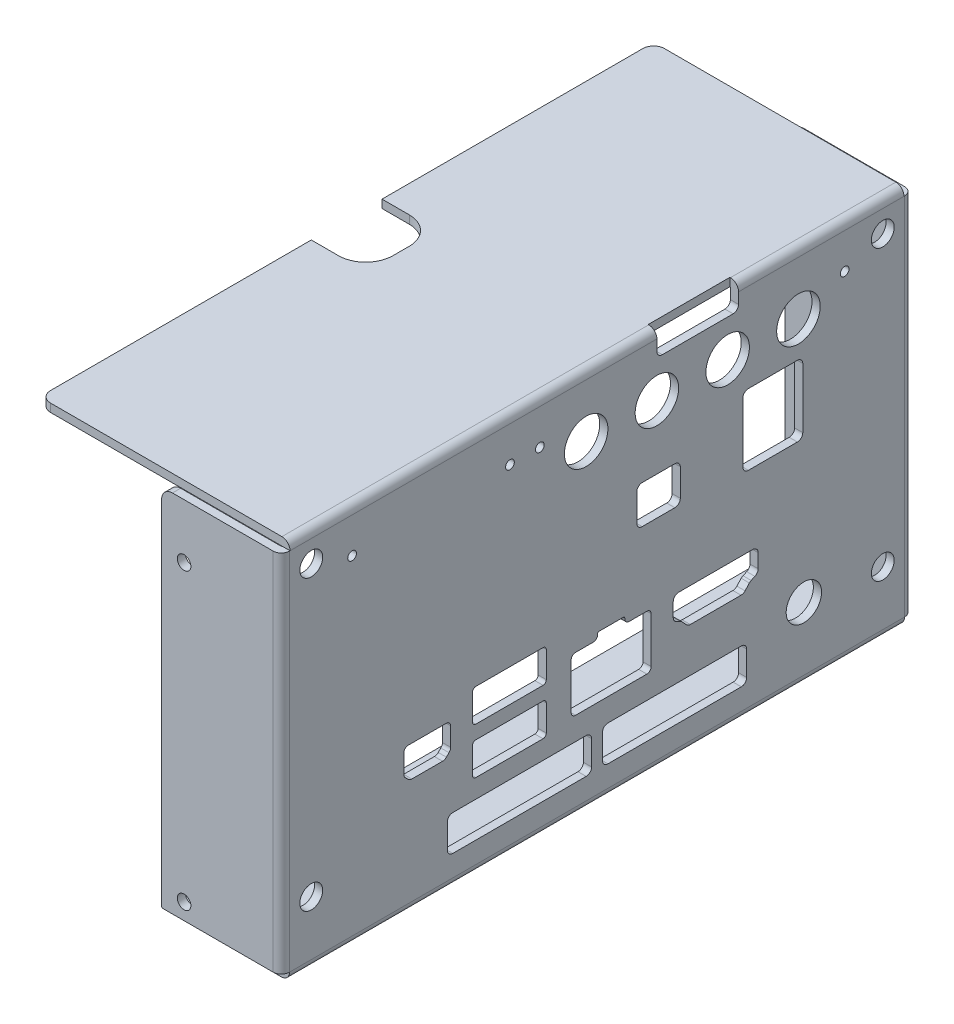
SolidWorks part; units mm, degrees
ref_plane "Alzado" through (0, 0, 0) normal (0, 0, 1) x (1, 0, 0)
ref_plane "Planta" through (0, 0, 0) normal (0, 1, 0) x (1, 0, 0)
ref_plane "Vista lateral" through (0, 0, 0) normal (1, 0, 0) x (0, 0, -1)
ref_plane "Plano4" through (57.5, 0, 0) normal (1, 0, 0) x (0, 0, -1)
sketch "Croquis1" plane through (57.5, 0, 0) normal (1, 0, 0) x (0, 0, -1)
  line L0 (25, -47.5) -> (25, 22.5)
  line L1 (25, 22.5) -> (-57.4, 22.5)
  line L2 (-57.4, 22.5) -> (-57.4, -47.5)
  line L3 (-57.4, -47.5) -> (25, -47.5)
extrude "Saliente-Extruir1" add sketch "Croquis1" against normal blind 34
ref_plane "Plano5" through (56, 0, 0) normal (1, 0, 0) x (0, 0, -1)
sketch "Croquis2" plane through (56, 0, 0) normal (1, 0, 0) x (0, 0, -1)
  line L0 (25, -47.5) -> (25, 22.5)
  line L1 (25, 22.5) -> (10, 22.5)
  line L2 (10, 22.5) -> (10, -47.5)
  line L3 (10, -47.5) -> (25, -47.5)
extrude "Cortar-Extruir1" cut sketch "Croquis2" against normal blind 0.1
sketch "Croquis3" plane through (0, 22.5, 0) normal (0, 1, 0) x (-1, 0, 0)
  line L0 (-57.5, -10) -> (-57.5, -25)
  line L1 (-57.5, -25) -> (-56, -25)
  line L2 (-56, -25) -> (-56, -10)
  line L3 (-56, -10) -> (-57.5, -10)
extrude "Cortar-Extruir2" cut sketch "Croquis3" against normal blind 1.5
sketch "Croquis4" plane through (0, -47.5, 0) normal (0, -1, 0) x (1, 0, 0)
  line L0 (23.5, -25) -> (55.9, -25)
  line L1 (55.9, -25) -> (55.9, -10)
  line L2 (55.9, -10) -> (56, -10)
  line L3 (56, -10) -> (56, 57.4)
  line L4 (56, 57.4) -> (23.5, 57.4)
  line L5 (23.5, 57.4) -> (23.5, -25)
extrude "Cortar-Extruir3" cut sketch "Croquis4" against normal blind 68.5
sketch "Croquis5" plane through (0, 21, 0) normal (0, 1, 0) x (-1, 0, 0)
  line L0 (-57.5, -10) -> (-57.5, -25)
  line L1 (-57.5, -25) -> (-56, -25)
  line L2 (-56, -25) -> (-56, -10)
  line L3 (-56, -10) -> (-57.5, -10)
extrude "Cortar-Extruir4" cut sketch "Croquis5" against normal blind 3
sketch "Croquis6" plane through (0, 0, -25) normal (0, 0, -1) x (-1, 0, 0)
  line L0 (-57.5, 22.5) -> (-23.5, 22.5)
  line L1 (-23.5, 22.5) -> (-23.5, 21)
  line L2 (-23.5, 21) -> (-56, 21)
  line L3 (-56, 21) -> (-56, -47.5)
  line L4 (-56, -47.5) -> (-57.5, -47.5)
  line L5 (-57.5, -47.5) -> (-57.5, 22.5)
extrude "Saliente-Extruir2" add sketch "Croquis6" along normal blind 30.4
sketch "Croquis7" plane through (0, 0, -55.4) normal (0, 0, -1) x (-1, 0, 0)
  line L0 (-56, -47.5) -> (-57.5, -47.5)
  line L1 (-57.5, -47.5) -> (-57.5, 21)
  line L2 (-57.5, 21) -> (-56, 21)
  line L3 (-56, 21) -> (-56, -47.5)
extrude "Saliente-Extruir3" add sketch "Croquis7" along normal blind 1.6
sketch "Croquis8" plane through (56, 0, 0) normal (-1, 0, 0) x (0, 0, 1)
  line L0 (-55.5, 21) -> (-55.5, -47.5)
  line L1 (-55.5, -47.5) -> (-57, -47.5)
  line L2 (-57, -47.5) -> (-57, 21)
  line L3 (-57, 21) -> (-55.5, 21)
extrude "Saliente-Extruir4" add sketch "Croquis8" along normal blind 20.5
sketch "Croquis9" plane through (0, 0, 57.4) normal (0, 0, 1) x (1, 0, 0)
  line L0 (56, 21) -> (57.5, 21)
  line L1 (57.5, 21) -> (57.5, -47.5)
  line L2 (57.5, -47.5) -> (56, -47.5)
  line L3 (56, -47.5) -> (56, 21)
extrude "Saliente-Extruir5" add sketch "Croquis9" along normal blind 1.6
sketch "Croquis10" plane through (56, 0, 0) normal (-1, 0, 0) x (0, 0, 1)
  line L0 (59, 21) -> (59, -47.5)
  line L1 (59, -47.5) -> (57.5, -47.5)
  line L2 (57.5, -47.5) -> (57.5, 21)
  line L3 (57.5, 21) -> (59, 21)
extrude "Saliente-Extruir6" add sketch "Croquis10" along normal blind 20.5
sketch "Croquis33" plane through (23.5, 0, 0) normal (-1, 0, 0) x (0, 0, 1)
  line L1 (-55.4, 22.5) -> (57.4, 22.5)
  line L2 (-55.4, 22.5) -> (-55.4, 21)
  line L3 (-55.4, 21) -> (57.4, 21)
  line L4 (57.4, 22.5) -> (57.4, 21)
extrude "Saliente-Extruir7" add sketch "Croquis33" along normal blind 12
sketch "Croquis11" plane through (0, 21, 0) normal (0, -1, 0) x (1, 0, 0)
  line L0 (11.5, 7.5) -> (11.5, -5.5)
  line L1 (11.5, -5.5) -> (21.5, -5.5)
  line L2 (21.5, -5.5) -> (21.5, 7.5)
  line L3 (21.5, 7.5) -> (11.5, 7.5)
  line L4 (11.5, -55.4) -> (11.5, 57.4) construction
extrude "Cortar-Extruir5" cut sketch "Croquis11" against normal through all
sketch "Croquis12" plane through (57.5, 0, 0) normal (1, 0, 0) x (0, 0, -1)
  line L0 (14.3, -7.5) -> (14.3, -0.5)
  line L1 (14.3, -0.5) -> (6.3, -0.5)
  line L2 (6.3, -0.5) -> (6.3, -7.5)
  line L3 (6.3, -7.5) -> (14.3, -7.5)
extrude "Cortar-Extruir6" cut sketch "Croquis12" against normal through all
sketch "Croquis13" plane through (57.5, 0, 0) normal (1, 0, 0) x (0, 0, -1)
  line L0 (36.8, 4.7) -> (25.8, 4.7)
  line L1 (25.8, 4.7) -> (25.8, -8.3)
  line L2 (25.8, -8.3) -> (36.8, -8.3)
  line L3 (36.8, -8.3) -> (36.8, 4.7)
extrude "Cortar-Extruir7" cut sketch "Croquis13" against normal through all
sketch "Croquis14" plane through (57.5, 0, 0) normal (1, 0, 0) x (0, 0, -1)
  line L0 (15.7003, -27.5) -> (25.8997, -27.5)
  line L1 (25.8997, -27.5) -> (25.8997, -25.5109)
  line L2 (25.8997, -25.5109) -> (28.6, -25.5109)
  line L3 (28.6, -25.5109) -> (28.6, -21.3)
  line L4 (28.6, -21.3) -> (13, -21.3)
  line L5 (13, -21.3) -> (13, -25.5109)
  line L6 (13, -25.5109) -> (15.7003, -25.5109)
  line L7 (15.7003, -25.5109) -> (15.7003, -27.5)
extrude "Cortar-Extruir8" cut sketch "Croquis14" against normal through all
sketch "Croquis15" plane through (57.5, 0, 0) normal (1, 0, 0) x (0, 0, -1)
  line L0 (-23.875, -23.65) -> (-10.325, -23.65)
  line L1 (-10.325, -23.65) -> (-10.325, -17.65)
  line L2 (-10.325, -17.65) -> (-23.875, -17.65)
  line L3 (-23.875, -17.65) -> (-23.875, -23.65)
extrude "Cortar-Extruir9" cut sketch "Croquis15" against normal through all
sketch "Croquis16" plane through (57.5, 0, 0) normal (1, 0, 0) x (0, 0, -1)
  line L0 (-23.875, -32.15) -> (-10.325, -32.15)
  line L1 (-10.325, -32.15) -> (-10.325, -26.15)
  line L2 (-10.325, -26.15) -> (-23.875, -26.15)
  line L3 (-23.875, -26.15) -> (-23.875, -32.15)
extrude "Cortar-Extruir10" cut sketch "Croquis16" against normal through all
sketch "Croquis17" plane through (57.5, 0, 0) normal (1, 0, 0) x (0, 0, -1)
  line L0 (-5.75, -31.4) -> (8.95, -31.4)
  line L1 (8.95, -31.4) -> (8.95, -21.4)
  line L2 (8.95, -21.4) -> (4.1, -21.4)
  line L3 (4.1, -21.4) -> (4.1, -20.2)
  line L4 (4.1, -20.2) -> (-0.9, -20.2)
  line L5 (-0.9, -20.2) -> (-0.9, -21.4)
  line L6 (-0.9, -21.4) -> (-5.75, -21.4)
  line L7 (-5.75, -21.4) -> (-5.75, -31.4)
extrude "Cortar-Extruir11" cut sketch "Croquis17" against normal through all
sketch "Croquis18" plane through (57.5, 0, 0) normal (1, 0, 0) x (0, 0, -1)
  line L0 (-28.5, -35.6) -> (-28.5, -42.1)
  line L1 (-28.5, -42.1) -> (-2, -42.1)
  line L2 (-2, -42.1) -> (-2, -35.6)
  line L3 (-2, -35.6) -> (-28.5, -35.6)
extrude "Cortar-Extruir12" cut sketch "Croquis18" against normal through all
sketch "Croquis19" plane through (57.5, 0, 0) normal (1, 0, 0) x (0, 0, -1)
  line L0 (0, -42.1) -> (26.5, -42.1)
  line L1 (26.5, -42.1) -> (26.5, -35.6)
  line L2 (26.5, -35.6) -> (0, -35.6)
  line L3 (0, -35.6) -> (0, -42.1)
extrude "Cortar-Extruir13" cut sketch "Croquis19" against normal through all
sketch "Croquis20" plane through (56, 0, 0) normal (-1, 0, 0) x (0, 0, 1)
  line L0 (35.4349, -26.5) -> (36.5, -25.4349)
  line L1 (36.5, -25.4349) -> (36.5, -20.8)
  line L2 (36.5, -20.8) -> (27.9, -20.8)
  line L3 (27.9, -20.8) -> (27.9, -25.4349)
  line L4 (27.9, -25.4349) -> (28.9651, -26.5)
  line L5 (28.9651, -26.5) -> (35.4349, -26.5)
extrude "Cortar-Extruir14" cut sketch "Croquis20" against normal through all
draft "Ángulo de salida1" type of draft neutral plane draft angle 23.88 faces to draft 1 face at (56.75, -25.5109, -27.2498) neutral plane through (11.5, -25.5109, -28.6) neutral plane normal (0, 0, 1) parameters "D1"=23.88
draft "Ángulo de salida2" type of draft neutral plane draft angle 23.88 faces to draft 1 face at (56.75, -25.5109, -14.3502) neutral plane through (11.5, -21.3, -13) neutral plane normal (0, 0, -1) parameters "D1"=23.88
draft "Ángulo de salida3" type of draft neutral plane draft angle 42.53 faces to draft 2 face at (56.75, -27.1032, -25.8997) face at (56.75, -27.1032, -15.7003) neutral plane through (11.5, -27.5, -15.7003) neutral plane normal (0, 1, 0) parameters "D1"=42.53
hole_wizard "Diámetro de taladro Ø8.0 (8)1" positions "Croquis22" profile "Croquis21" hole size "Ø8.0" standard "Ansi Metric"
sketch "Croquis22" plane through (56, 0, 0) normal (-1, 0, 0) x (0, 0, 1)
  point P0 (-23, 11.2)
  point P1 (3, 11.2)
  point P2 (-36, 11.2)
  point P3 (-10, 11.2)
sketch "Croquis21" plane through (56, 11.2, -23) normal (0, 1, 0) x (0, 0, 1)
  line L0 (0, 0) -> (0, 1.5)
  line L1 (0, 1.5) -> (4, 1.5)
  line L2 (4, 1.5) -> (4, 0)
  line L5 (4, 0) -> (0, 0)
  line L11 (0, -6.35) -> (0, 107.95) construction
  dimension "Diámetro de taladro hasta el siguiente" = 8
  dimension "Profundidad de taladro hasta el siguiente" = 1.5
hole_wizard "Diámetro de taladro Ø6.5 (6.5)1" positions "Croquis24" profile "Croquis23" hole size "Ø6.5" standard "Ansi Metric"
sketch "Croquis24" plane through (56, 0, 0) normal (-1, 0, 0) x (0, 0, 1)
  point P0 (-37, -34.4)
sketch "Croquis23" plane through (56, -34.4, -37) normal (0, 1, 0) x (0, 0, 1)
  line L0 (0, 0) -> (0, 1.5)
  line L1 (0, 1.5) -> (3.25, 1.5)
  line L2 (3.25, 1.5) -> (3.25, 0)
  line L5 (3.25, 0) -> (0, 0)
  line L11 (0, -6.35) -> (0, 107.95) construction
  dimension "Diámetro de taladro hasta el siguiente" = 6.5
  dimension "Profundidad de taladro hasta el siguiente" = 1.5
hole_wizard "Diámetro de taladro Ø2.5 (2.5)1" positions "Croquis26" profile "Croquis25" hole size "Ø2.5" standard "Ansi Metric" end condition through all
sketch "Croquis26" plane through (0, 0, 57.5) normal (0, 0, -1) x (-1, 0, 0)
  line L0 (-56, 38.5) -> (-56, -38.5) construction
  point P0 (-39.63, -43)
  point P1 (-39.63, 11)
  point P2 (0, 0)
  point P3 (0, 0)
  point P6 (0, 0)
  dimension "D1" = 16.37
sketch "Croquis25" plane through (39.63, -43, 57.5) normal (1, 0, 0) x (0, 1, 0)
  line L0 (0, 0) -> (0, 1.5)
  line L1 (0, 1.5) -> (1.25, 1.5)
  line L2 (1.25, 1.5) -> (1.25, 0)
  line L5 (1.25, 0) -> (0, 0)
  line L11 (0, -6.35) -> (0, 107.95) construction
  point P3 (0, 0)
  dimension "Diámetro de taladro hasta el siguiente" = 2.5
  dimension "Profundidad de taladro hasta el siguiente" = 1.5
hole_wizard "Diámetro de taladro Ø2.5 (2.5)2" positions "Croquis28" profile "Croquis27" hole size "Ø2.5" standard "Ansi Metric"
sketch "Croquis28" plane through (0, 0, -55.5) normal (0, 0, 1) x (1, 0, 0)
  line L0 (56, -38.5) -> (56, 38.5) construction
  point P0 (39.63, -43)
  point P1 (39.63, 11)
  point P2 (0, 0)
  point P3 (40.299, 11.2212)
  point P4 (40.299, -42.3595)
  point P5 (40.299, 11.2278)
  point P6 (0, 0)
  point P9 (0, 0)
  point P11 (0, 0)
  dimension "D1" = 16.37
sketch "Croquis27" plane through (39.63, -43, -55.5) normal (1, 0, 0) x (0, -1, 0)
  line L0 (0, 0) -> (0, 1.5)
  line L1 (0, 1.5) -> (1.25, 1.5)
  line L2 (1.25, 1.5) -> (1.25, 0)
  line L5 (1.25, 0) -> (0, 0)
  line L11 (0, -6.35) -> (0, 107.95) construction
  dimension "Diámetro de taladro hasta el siguiente" = 2.5
  dimension "Profundidad de taladro hasta el siguiente" = 1.5
hole_wizard "Diámetro de taladro Ø4.2 (4.2)1" positions "Croquis30" profile "Croquis29" hole size "Ø4.2" standard "Ansi Metric"
sketch "Croquis30" plane through (56, 0, 0) normal (-1, 0, 0) x (0, 0, 1)
  point P0 (53.5, 17)
  point P1 (53.5, -36)
  point P2 (-51.5, 17)
  point P3 (-51.5, -36)
sketch "Croquis29" plane through (56, 17, 53.5) normal (0, 1, 0) x (0, 0, 1)
  line L0 (0, 0) -> (0, 1.5)
  line L1 (0, 1.5) -> (2.1, 1.5)
  line L2 (2.1, 1.5) -> (2.1, 0)
  line L5 (2.1, 0) -> (0, 0)
  line L11 (0, -6.35) -> (0, 107.95) construction
  dimension "Diámetro de taladro hasta el siguiente" = 4.2
  dimension "Profundidad de taladro hasta el siguiente" = 1.5
hole_wizard "Diámetro de taladro Ø1.6 (1.6)1" positions "Croquis32" profile "Croquis31" hole size "Ø1.6" standard "Ansi Metric"
sketch "Croquis32" plane through (56, 0, 0) normal (-1, 0, 0) x (0, 0, 1)
  point P0 (11.5, 14.5)
  point P1 (-44.5, 14.5)
  point P2 (46, 14.5)
  point P3 (17, 14.5)
sketch "Croquis31" plane through (56, 14.5, 11.5) normal (0, 1, 0) x (0, 0, 1)
  line L0 (0, 0) -> (0, 1.5)
  line L1 (0, 1.5) -> (0.8, 1.5)
  line L2 (0.8, 1.5) -> (0.8, 0)
  line L5 (0.8, 0) -> (0, 0)
  line L11 (0, -6.35) -> (0, 107.95) construction
  dimension "Diámetro de taladro hasta el siguiente" = 1.6
  dimension "Profundidad de taladro hasta el siguiente" = 1.5
fillet "Redondeo1" radius 0.3 2 edges at (56.75, -20.2, -4.1) (56.75, -20.2, 0.9) tangent propagation no
fillet "Redondeo2" radius 0.6 8 edges at (56.75, -32.15, 23.875) (56.75, -26.15, 10.325) (56.75, -26.15, 23.875) (56.75, -17.65, 23.875) (56.75, -32.15, 10.325) (56.75, -17.65, 10.325) (56.75, -23.65, 23.875) (56.75, -23.65, 10.325) tangent propagation no
fillet "Redondeo3" radius 0.8 8 edges at (56.75, -20.8, 27.9) (56.75, -20.8, 36.5) (56.75, -21.4, -8.95) (56.75, -21.4, 5.75) (56.75, -31.4, -8.95) (56.75, -21.4, 0.9) (56.75, -21.4, -4.1) (56.75, -31.4, 5.75) tangent propagation no
fillet "Redondeo4" radius 1 30 edges at (56.75, -42.1, 2) (56.75, -25.4349, 27.9) (56.75, -21.3, -28.6) (56.75, -35.6, 28.5) (56.75, -35.6, -26.5) (56.75, -8.3, -36.8) (56.75, -42.1, 0) (56.75, -26.5, 35.4349) (56.75, -25.4349, 36.5) (56.75, -25.5109, -13) (56.75, -26.5, 28.9651) (56.75, -26.1637, -27.1255) (56.75, -27.5, -15.7003) (56.75, 18, -25) (56.75, -21.3, -13) (56.75, 18, -10) (56.75, -25.5109, -28.6) (56.75, -7.5, -6.3) (56.75, -27.5, -25.8997) (56.75, -0.5, -6.3) (56.75, -35.6, 2) (56.75, -0.5, -14.3) (56.75, -42.1, 28.5) (56.75, -7.5, -14.3) (56.75, -35.6, 0) (56.75, 4.7, -36.8) (56.75, -42.1, -26.5) (56.75, 4.7, -25.8) (56.75, -8.3, -25.8) (56.75, -26.1637, -14.4745) tangent propagation no
fillet "Redondeo5" radius 1.5 4 edges at (57.5, -13.25, 59) (57.5, 22.5, 23.7) (57.5, 22.5, -40.2) (57.5, -13.25, -57) tangent propagation no
fillet "Redondeo6" radius 2 6 edges at (35.5, 21, -56.25) (35.5, 21, 58.25) (35.5, -47.5, 58.25) (35.5, -47.5, -56.25) (11.5, 21.75, 57.4) (11.5, 21.75, -55.4) tangent propagation no
fillet "Redondeo7" radius 5 2 edges at (21.5, 21.75, 7.5) (21.5, 21.75, -5.5) tangent propagation no
sketch "Croquis34" plane through (57.5, 0, 0) normal (1, 0, 0) x (0, 0, -1)
  line L0 (57, 21) -> (57, -47.5) construction
  line L1 (-59, -47.5) -> (57, -47.5)
  line L2 (-59, -47.5) -> (-59, -46)
  line L3 (-59, -46) -> (57, -46)
  line L4 (57, -47.5) -> (57, -46)
  dimension "D1" = 1.5
extrude "Cortar-Extruir15" cut sketch "Croquis34" against normal through all
sketch "Croquis35" plane through (57.5, 0, 0) normal (1, 0, 0) x (0, 0, -1)
  line L0 (55.5, -46) -> (55.5, 21) construction
  line L1 (-57.5, -46) -> (55.5, -46)
  line L2 (-57.5, -46) -> (-57.5, -47.5)
  line L3 (-57.5, -47.5) -> (55.5, -47.5)
  line L4 (55.5, -46) -> (55.5, -47.5)
  dimension "D1" = 1.5
extrude "Saliente-Extruir8" add sketch "Croquis35" against normal blind 22 separate body
fillet "Redondeo8" radius 1.5 1 edges at (57.5, -47.5, 1)
